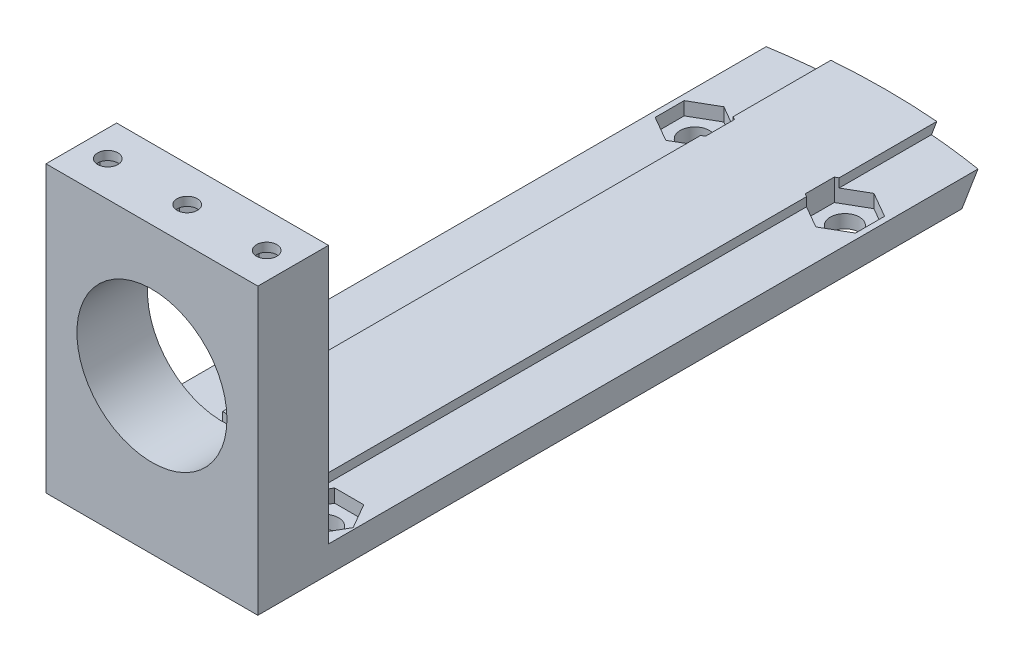
SolidWorks part; units mm, degrees
ref_plane "Front Plane" through (0, 0, 0) normal (0, 0, 1) x (1, 0, 0)
ref_plane "Top Plane" through (0, 0, 0) normal (0, 1, 0) x (1, 0, 0)
ref_plane "Right Plane" through (0, 0, 0) normal (1, 0, 0) x (0, 0, -1)
sketch "Sketch1" plane through (0, 0, 0) normal (0, 1, 0) x (1, 0, 0)
  line L1 (0, 0) -> (24, 0)
  line L2 (0, 0) -> (0, 81.5022)
  line L3 (0, 81.5022) -> (24, 81.5022)
  line L4 (24, 0) -> (24, 81.5022)
  dimension "D1" = 24
extrude "Boss-Extrude1" add sketch "Sketch1" along normal blind 3
sketch "Sketch2" plane through (0, 0, 0) normal (0, 1, 0) x (1, 0, 0)
  line L0 (0, 0) -> (24, 0) construction
  circle A0 centre (3.5, 3) radius 1.65
  circle A1 centre (12, 3) radius 1.65
  circle A2 centre (20.5, 3) radius 1.65
  circle A6 centre (3.5, 62) radius 1.65
  circle A8 centre (20.5, 62) radius 1.65
  circle A9 centre (12, 32.5) radius 1.65 [skipped]
  circle A10 centre (3.5, 32.5) radius 1.65 [skipped]
  circle A11 centre (20.5, 32.5) radius 1.65 [skipped]
  circle A12 centre (12, 62) radius 1.65 [skipped]
  point P9 (12, 0)
  dimension "D1" = 3.3
  dimension "D2" = 3
  dimension "D3" = 8.5
  dimension "D4" = 8.5
  dimension "D5" = 3
  dimension "D6" = 59
extrude "Cut-Extrude1" cut sketch "Sketch2" along normal through all
sketch "Sketch3" plane through (0, 0, 0) normal (0, 0, 1) x (1, 0, 0)
  line L0 (0, 3) -> (24, 3) construction
  line L1 (6, 3) -> (18, 3)
  line L2 (6, 3) -> (6, 4)
  line L3 (6, 4) -> (18, 4)
  line L4 (18, 3) -> (18, 4)
  line L5 (77.5014, 4) -> (-53.5014, 4) construction
  point P11 (12, 3)
  dimension "D1" = 12
  dimension "D2" = 12
extrude "Boss-Extrude2" add sketch "Sketch3" against normal up to surface (81.5022 mm away) from offset 6 up to face at (12, 1.5, -81.5022) offset against normal yes
ref_plane "Plane1" through (12, 0, 0) normal (-1, 0, 0) x (0, 0, 1)
sketch "Sketch4" plane through (12, 0, 0) normal (1, 0, 0) x (0, 0, -1)
  line L0 (94.4965, 36.2415) -> (19.4137, -88.8964)
  line L1 (19.4137, -88.8964) -> (139.5903, -88.8964)
  line L2 (139.5903, -88.8964) -> (139.5903, 36.2415)
  line L3 (139.5903, 36.2415) -> (94.4965, 36.2415)
  line L4 (73, -6) -> (79, 4) construction
  line L6 (0, 0) -> (0, 3) construction
  dimension "D1" = 3.3
revolve "Cut-Revolve1" cut sketch "Sketch4" angle 360 about L6
sketch "Sketch5" plane through (0, 3, 0) normal (0, 1, 0) x (1, 0, 0)
  line L0 (18, 74.3097) -> (18, 6) construction
  line L1 (15.2909, 3) -> (13.6454, 5.85)
  line L2 (13.6454, 5.85) -> (10.3546, 5.85)
  line L3 (10.3546, 5.85) -> (8.7091, 3)
  line L4 (8.7091, 3) -> (10.3546, 0.15)
  line L5 (10.3546, 0.15) -> (13.6454, 0.15)
  line L6 (13.6454, 0.15) -> (15.2909, 3)
  line L7 (23.7909, 3) -> (22.1454, 5.85)
  line L8 (22.1454, 5.85) -> (18.8546, 5.85)
  line L9 (18.8546, 5.85) -> (17.2091, 3)
  line L10 (17.2091, 3) -> (18.8546, 0.15)
  line L11 (18.8546, 0.15) -> (22.1454, 0.15)
  line L12 (22.1454, 0.15) -> (23.7909, 3)
  line L13 (6.7909, 3) -> (5.1454, 5.85)
  line L14 (5.1454, 5.85) -> (1.8546, 5.85)
  line L15 (1.8546, 5.85) -> (0.2091, 3)
  line L16 (0.2091, 3) -> (1.8546, 0.15)
  line L17 (1.8546, 0.15) -> (5.1454, 0.15)
  line L18 (5.1454, 0.15) -> (6.7909, 3)
  line L31 (6.35, 63.6454) -> (3.5, 65.2909)
  line L32 (3.5, 65.2909) -> (0.65, 63.6454)
  line L33 (0.65, 63.6454) -> (0.65, 60.3546)
  line L34 (0.65, 60.3546) -> (3.5, 58.7091)
  line L35 (3.5, 58.7091) -> (6.35, 60.3546)
  line L36 (6.35, 60.3546) -> (6.35, 63.6454)
  line L37 (23.35, 63.6454) -> (20.5, 65.2909)
  line L38 (20.5, 65.2909) -> (17.65, 63.6454)
  line L39 (17.65, 63.6454) -> (17.65, 60.3546)
  line L40 (17.65, 60.3546) -> (20.5, 58.7091)
  line L41 (20.5, 58.7091) -> (23.35, 60.3546)
  line L42 (23.35, 60.3546) -> (23.35, 63.6454)
  line L43 (6, 74.3097) -> (6, 6) construction
  circle A0 centre (12, 3) radius 2.85 construction
  circle A1 centre (20.5, 3) radius 2.85 construction
  circle A2 centre (3.5, 3) radius 2.85 construction
  circle A3 centre (3.5, 62) radius 2.85 construction
  circle A4 centre (20.5, 62) radius 2.85 construction
  dimension "D1" = 5.7
  dimension "D2" = 5.7
extrude "Cut-Extrude2" cut sketch "Sketch5" against normal blind 1.5 and the other way through all
sketch "Sketch6" plane through (0, 0, 0) normal (0, 0, 1) x (1, 0, 0)
  line L0 (12, 2.2) -> (12, -2.2) construction
  line L1 (0, 0) -> (24, 0)
  line L2 (0, 0) -> (0, 32.3)
  line L3 (0, 32.3) -> (24, 32.3)
  line L4 (24, 0) -> (24, 32.3)
  circle A0 centre (12, 17.5) radius 8.5
  dimension "D2" = 17
  dimension "D1" = 32.3
  dimension "D3" = 17.5
extrude "Boss-Extrude3" add sketch "Sketch6" along normal blind 8
sketch "Sketch9" plane through (0, 32.3, 0) normal (0, 1, 0) x (1, 0, 0)
  line L0 (0, -4) -> (6, -4) construction
  line L1 (0, -8) -> (0, 0) construction
  line L2 (6, -4) -> (9, -4) construction
  line L3 (9, -4) -> (15, -4) construction
  line L4 (15, -4) -> (18, -4) construction
  line L5 (18, -4) -> (24, -4) construction
  line L6 (24, -8) -> (24, 0) construction
  circle A0 centre (3, -4) radius 1.15
  circle A1 centre (12, -4) radius 1.15
  circle A2 centre (21, -4) radius 1.15
  dimension "D1" = 2.3
  dimension "D2" = 6
extrude "Cut-Extrude3" cut sketch "Sketch9" against normal blind 5
sketch "Sketch10" plane through (0, 32.3, 0) normal (0, 1, 0) x (1, 0, 0)
  line L1 (3, -6.4249) -> (5.1, -5.2124)
  line L2 (5.1, -5.2124) -> (5.1, -2.7876)
  line L3 (5.1, -2.7876) -> (3, -1.5751)
  line L4 (3, -1.5751) -> (0.9, -2.7876)
  line L5 (0.9, -2.7876) -> (0.9, -5.2124)
  line L6 (0.9, -5.2124) -> (3, -6.4249)
  line L7 (12, -6.4249) -> (14.1, -5.2124)
  line L8 (14.1, -5.2124) -> (14.1, -2.7876)
  line L9 (14.1, -2.7876) -> (12, -1.5751)
  line L10 (12, -1.5751) -> (9.9, -2.7876)
  line L11 (9.9, -2.7876) -> (9.9, -5.2124)
  line L12 (9.9, -5.2124) -> (12, -6.4249)
  line L13 (21, -6.4249) -> (23.1, -5.2124)
  line L14 (23.1, -5.2124) -> (23.1, -2.7876)
  line L15 (23.1, -2.7876) -> (21, -1.5751)
  line L16 (21, -1.5751) -> (18.9, -2.7876)
  line L17 (18.9, -2.7876) -> (18.9, -5.2124)
  line L18 (18.9, -5.2124) -> (21, -6.4249)
  circle A0 centre (3, -4) radius 2.1 construction
  circle A1 centre (12, -4) radius 2.1 construction
  circle A2 centre (21, -4) radius 2.1 construction
  dimension "D1" = 4.2
extrude "Cut-Extrude4" cut sketch "Sketch10" against normal blind 1.8 from offset 1 offset against normal yes
